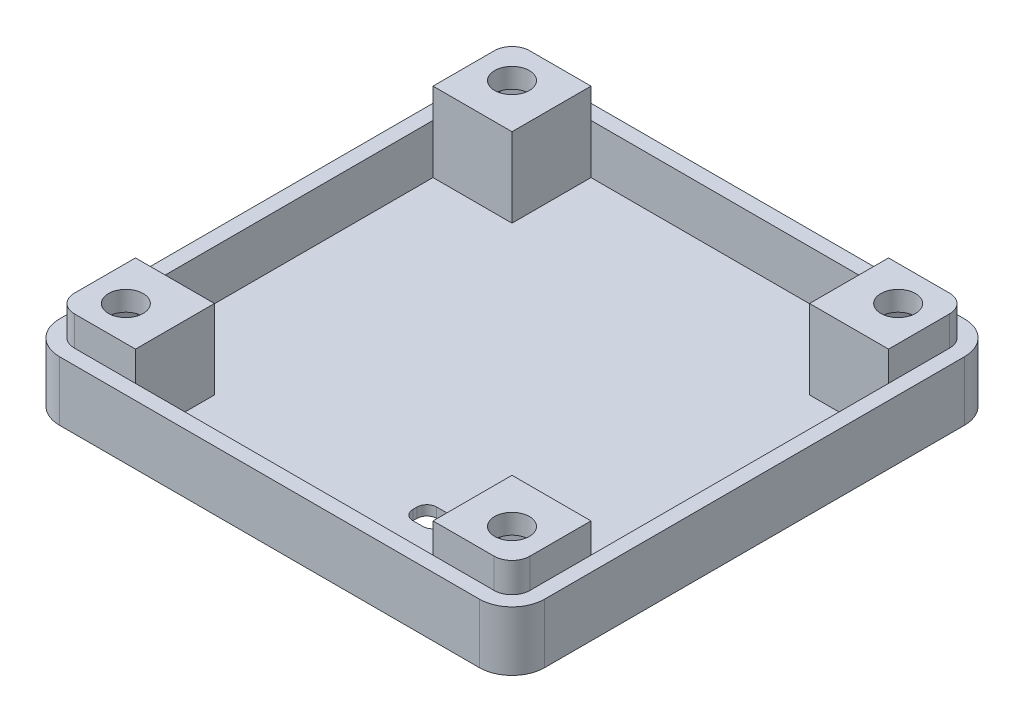
SolidWorks part; units mm, degrees
note: The reader was unsure of these and kept them because the rebuilt part matched: shared geometry of "草图1<3>".
ref_plane "前视基准面" through (0, 0, 0) normal (0, 0, 1) x (1, 0, 0)
ref_plane "上视基准面" through (0, 0, 0) normal (0, 1, 0) x (1, 0, 0)
ref_plane "右视基准面" through (0, 0, 0) normal (1, 0, 0) x (0, 0, -1)
other "Configuration Table"
sketch "草图1" plane through (0, 0, 0) normal (0, 1, 0) x (1, 0, 0)
  line L0 (-21.2, -23) -> (21.2, -23)
  line L1 (-23, -21.2) -> (-23, 21.2)
  line L2 (-21.2, 23) -> (21.2, 23)
  line L3 (23, -21.2) -> (23, 21.2)
  line L4 (-23, -23) -> (23, 23) construction
  line L5 (-23, 23) -> (23, -23) construction
  arc A0 (21.2, 23) -> (23, 21.2) centre (21.2, 21.2) cw
  arc A1 (23, -21.2) -> (21.2, -23) centre (21.2, -21.2) cw
  arc A2 (-21.2, -23) -> (-23, -21.2) centre (-21.2, -21.2) cw
  arc A3 (-23, 21.2) -> (-21.2, 23) centre (-21.2, 21.2) cw
  circle A4 centre (-19.5, 19.5) radius 1.75
  circle A8 centre (19.5, 19.5) radius 1.75
  circle A9 centre (19.5, -19.5) radius 1.75
  circle A10 centre (-19.5, -19.5) radius 1.75
  point P0 (0, 0)
  point P25 (0, 0)
  point P36 (0, 0)
  dimension "D3" = 1.8
  dimension "D5" = 3.5
  dimension "D1" = 46
  dimension "D2" = 46
  dimension "D4" = 3.5
  dimension "D6" = 4
extrude "拉伸-薄壁1" add sketch "草图1" along normal blind 6 thin contours A3 L1 A2 L0 A1 L3 A0 L2 A10 A9 A8 A4 | A10 | A4 | A8 | A9
extrude "凸台-拉伸1" add sketch "草图1<3>" along normal blind 9
sketch "草图1<3>" plane through (0, 0, 0) normal (0, 1, 0) x (1, 0, 0) same geometry as "草图1"
sketch "草图2" plane through (0, 0, 0) normal (0, -1, 0) x (1, 0, 0)
  line L0 (22.35, 17.8546) -> (22.35, 21.1454)
  line L1 (-17.8546, 22.35) -> (-21.1454, 22.35)
  line L2 (-21.1454, 22.35) -> (-22.7909, 19.5)
  line L3 (-22.7909, 19.5) -> (-21.1454, 16.65)
  line L4 (-21.1454, 16.65) -> (-17.8546, 16.65)
  line L5 (-17.8546, 16.65) -> (-16.2091, 19.5)
  line L6 (-16.2091, 19.5) -> (-17.8546, 22.35)
  line L7 (22.35, 21.1454) -> (19.5, 22.7909)
  line L8 (19.5, 22.7909) -> (16.65, 21.1454)
  line L9 (16.65, 21.1454) -> (16.65, 17.8546)
  line L10 (16.65, 17.8546) -> (19.5, 16.2091)
  line L11 (19.5, 16.2091) -> (22.35, 17.8546)
  line L12 (17.8546, -22.35) -> (21.1454, -22.35)
  line L13 (21.1454, -22.35) -> (22.7909, -19.5)
  line L14 (22.7909, -19.5) -> (21.1454, -16.65)
  line L15 (21.1454, -16.65) -> (17.8546, -16.65)
  line L16 (17.8546, -16.65) -> (16.2091, -19.5)
  line L17 (16.2091, -19.5) -> (17.8546, -22.35)
  line L18 (-22.35, -17.8546) -> (-22.35, -21.1454)
  line L19 (-22.35, -21.1454) -> (-19.5, -22.7909)
  line L20 (-19.5, -22.7909) -> (-16.65, -21.1454)
  line L21 (-16.65, -21.1454) -> (-16.65, -17.8546)
  line L22 (-16.65, -17.8546) -> (-19.5, -16.2091)
  line L23 (-19.5, -16.2091) -> (-22.35, -17.8546)
  circle A0 centre (-19.5, 19.5) radius 2.85 construction
  circle A1 centre (19.5, 19.5) radius 2.85 construction
  circle A2 centre (19.5, -19.5) radius 2.85 construction
  circle A3 centre (-19.5, -19.5) radius 2.85 construction
  point P36 (0, 0)
  dimension "D1" = 5.7
  dimension "D2" = 4
extrude "切除-拉伸1" cut sketch "草图2" against normal blind 7
sketch "草图3" plane through (0, 9, 0) normal (0, 1, 0) x (1, 0, 0)
  line L1 (-15.024, -23) -> (15.024, -23)
  line L2 (-15.024, -23) -> (-15.024, 23)
  line L3 (-15.024, 23) -> (15.024, 23)
  line L4 (15.024, -23) -> (15.024, 23)
  line L5 (-15.024, -23) -> (15.024, 23) construction
  line L6 (-15.024, 23) -> (15.024, -23) construction
  line L8 (-23, -15.024) -> (23, -15.024)
  line L9 (-23, -15.024) -> (-23, 15.024)
  line L10 (-23, 15.024) -> (23, 15.024)
  line L11 (23, -15.024) -> (23, 15.024)
  line L12 (-23, -15.024) -> (23, 15.024) construction
  line L13 (-23, 15.024) -> (23, -15.024) construction
  point P0 (0, 0)
  point P9 (0, 0)
extrude "切除-拉伸2" cut sketch "草图3" against normal blind 8
sketch "草图5" plane through (0, 0, 0) normal (0, -1, 0) x (-1, 0, 0)
  line L0 (21.2, -24.5) -> (-21.2, -24.5) construction
  line L1 (-6, -13.6) -> (-7, -13.6)
  line L2 (-5, -14.6) -> (-5, -15)
  line L3 (-6, -16) -> (-7, -16)
  line L4 (-8, -14.6) -> (-8, -15)
  line L5 (-5, -13.6) -> (-8, -16) construction
  line L6 (-5, -16) -> (-8, -13.6) construction
  line L7 (-24.5, -21.2) -> (-24.5, 21.2) construction
  arc A0 (-5, -14.6) -> (-6, -13.6) centre (-6, -14.6) ccw
  arc A1 (-6, -16) -> (-5, -15) centre (-6, -15) ccw
  arc A2 (-8, -15) -> (-7, -16) centre (-7, -15) ccw
  arc A3 (-8, -14.6) -> (-7, -13.6) centre (-7, -14.6) cw
  point P0 (-6.5, -14.8)
  dimension "D5" = 1
  dimension "D1" = 9.7
  dimension "D2" = 18
  dimension "D3" = 2.4
  dimension "D4" = 3
extrude "切除-拉伸3" cut sketch "草图5" against normal blind 5
